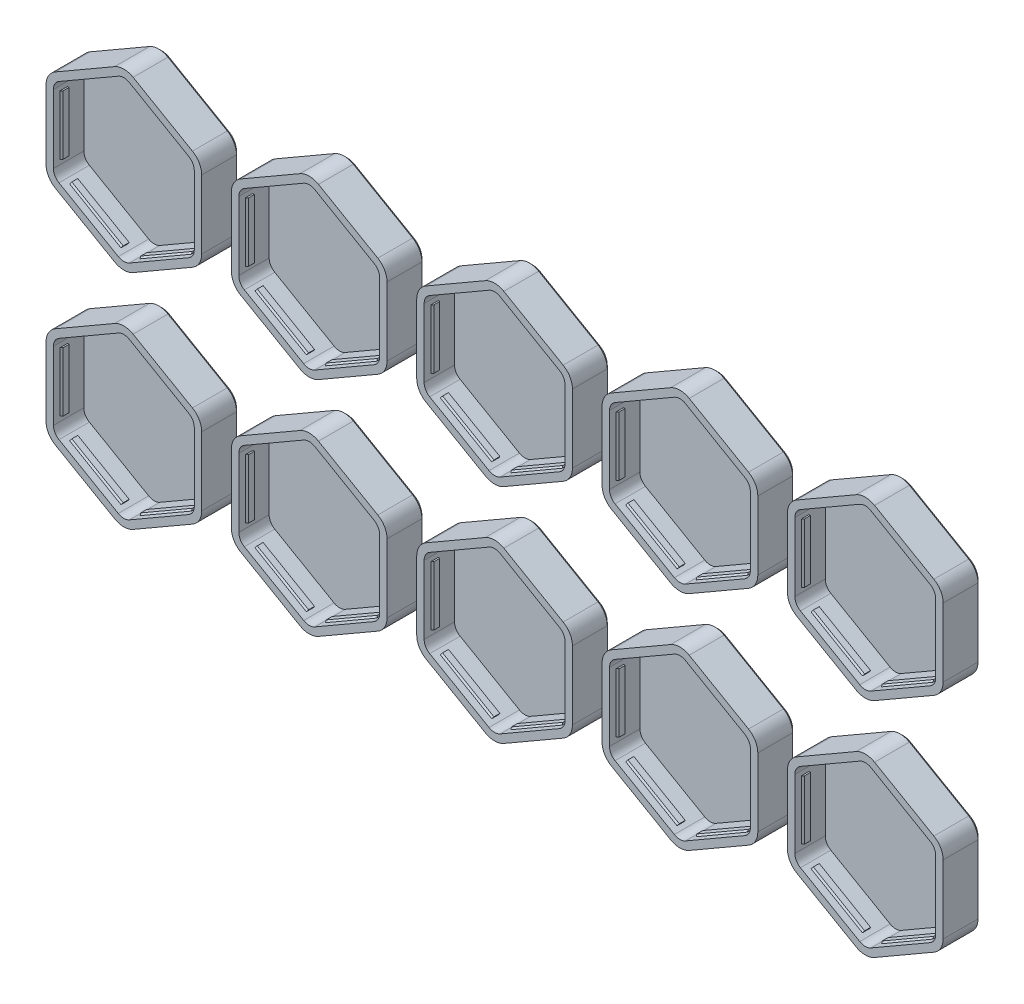
SolidWorks part; units mm, degrees
ref_plane "前视基准面" through (0, 0, 0) normal (0, 0, 1) x (1, 0, 0)
ref_plane "上视基准面" through (0, 0, 0) normal (0, 1, 0) x (1, 0, 0)
ref_plane "右视基准面" through (0, 0, 0) normal (1, 0, 0) x (0, 0, -1)
sketch "草图1" plane through (0, 0, 0) normal (0, 0, 1) x (1, 0, 0)
  line L0 (-36.9964, 0) -> (135.3315, 0) construction
  line L8 (-20.6295, 11.6625) -> (-28.6295, 7.0437)
  line L9 (-30.0295, 4.6188) -> (-30.0295, -4.6188)
  line L10 (-28.6295, -7.0437) -> (-20.6295, -11.6625)
  line L11 (-17.8295, -11.6625) -> (-9.8295, -7.0437)
  line L12 (-8.4295, -4.6188) -> (-8.4295, 4.6188)
  line L13 (-9.8295, 7.0437) -> (-17.8295, 11.6625)
  line L14 (17.8795, 11.5759) -> (9.8795, 6.9571)
  line L15 (8.5295, 4.6188) -> (8.5295, -4.6188)
  line L16 (9.8795, -6.9571) -> (17.8795, -11.5759)
  line L17 (20.5795, -11.5759) -> (28.5795, -6.9571)
  line L18 (29.9295, -4.6188) -> (29.9295, 4.6188)
  line L19 (28.5795, 6.9571) -> (20.5795, 11.5759)
  line L20 (53.7572, 11.4893) -> (45.7572, 6.8705)
  line L21 (44.4572, 4.6188) -> (44.4572, -4.6188)
  line L22 (45.7572, -6.8705) -> (53.7572, -11.4893)
  line L23 (56.3572, -11.4893) -> (64.3572, -6.8705)
  line L24 (65.6572, -4.6188) -> (65.6572, 4.6188)
  line L25 (64.3572, 6.8705) -> (56.3572, 11.4893)
  line L26 (86.3289, 11.4027) -> (78.3289, 6.7839)
  line L27 (77.0789, 4.6188) -> (77.0789, -4.6188)
  line L28 (78.3289, -6.7839) -> (86.3289, -11.4027)
  line L29 (88.8289, -11.4027) -> (96.8289, -6.7839)
  line L30 (98.0789, -4.6188) -> (98.0789, 4.6188)
  line L31 (96.8289, 6.7839) -> (88.8289, 11.4027)
  circle A0 centre (-19.2295, 0) radius 10.8 construction
  circle A1 centre (19.2295, 0) radius 10.7 construction
  circle A2 centre (55.0572, 0) radius 10.6 construction
  circle A3 centre (87.5789, 0) radius 10.5 construction
  arc A4 (-8.4295, 4.6188) -> (-9.8295, 7.0437) centre (-11.2295, 4.6188) ccw
  arc A5 (-8.4295, -4.6188) -> (-9.8295, -7.0437) centre (-11.2295, -4.6188) cw
  arc A6 (-17.8295, -11.6625) -> (-20.6295, -11.6625) centre (-19.2295, -9.2376) cw
  arc A7 (-28.6295, -7.0437) -> (-30.0295, -4.6188) centre (-27.2295, -4.6188) cw
  arc A8 (-28.6295, 7.0437) -> (-30.0295, 4.6188) centre (-27.2295, 4.6188) ccw
  arc A9 (-20.6295, 11.6625) -> (-17.8295, 11.6625) centre (-19.2295, 9.2376) cw
  arc A10 (29.9295, 4.6188) -> (28.5795, 6.9571) centre (27.2295, 4.6188) ccw
  arc A11 (29.9295, -4.6188) -> (28.5795, -6.9571) centre (27.2295, -4.6188) cw
  arc A12 (20.5795, -11.5759) -> (17.8795, -11.5759) centre (19.2295, -9.2376) cw
  arc A13 (9.8795, -6.9571) -> (8.5295, -4.6188) centre (11.2295, -4.6188) cw
  arc A14 (8.5295, 4.6188) -> (9.8795, 6.9571) centre (11.2295, 4.6188) cw
  arc A15 (20.5795, 11.5759) -> (17.8795, 11.5759) centre (19.2295, 9.2376) ccw
  arc A16 (53.7572, 11.4893) -> (56.3572, 11.4893) centre (55.0572, 9.2376) cw
  arc A17 (65.6572, 4.6188) -> (64.3572, 6.8705) centre (63.0572, 4.6188) ccw
  arc A18 (65.6572, -4.6188) -> (64.3572, -6.8705) centre (63.0572, -4.6188) cw
  arc A19 (56.3572, -11.4893) -> (53.7572, -11.4893) centre (55.0572, -9.2376) cw
  arc A20 (45.7572, -6.8705) -> (44.4572, -4.6188) centre (47.0572, -4.6188) cw
  arc A21 (44.4572, 4.6188) -> (45.7572, 6.8705) centre (47.0572, 4.6188) cw
  arc A22 (98.0789, 4.6188) -> (96.8289, 6.7839) centre (95.5789, 4.6188) ccw
  arc A23 (98.0789, -4.6188) -> (96.8289, -6.7839) centre (95.5789, -4.6188) cw
  arc A24 (88.8289, -11.4027) -> (86.3289, -11.4027) centre (87.5789, -9.2376) cw
  arc A25 (78.3289, -6.7839) -> (77.0789, -4.6188) centre (79.5789, -4.6188) cw
  arc A26 (77.0789, 4.6188) -> (78.3289, 6.7839) centre (79.5789, 4.6188) cw
  arc A27 (88.8289, 11.4027) -> (86.3289, 11.4027) centre (87.5789, 9.2376) ccw
  dimension "D1" = 21.6
  dimension "D2" = 21.4
  dimension "D3" = 21.2
  dimension "D4" = 21
  dimension "D5" = 2.8
  dimension "D6" = 2.7
  dimension "D7" = 2.6
  dimension "D8" = 2.5
extrude "凸台-拉伸1" add sketch "草图1" along normal blind 4.5
sketch "草图2" plane through (0, 0, 4.5) normal (0, 0, 1) x (1, 0, 0)
  line L0 (-30.0295, 0) -> (-8.4295, 0) construction
  line L1 (-30.0295, 4.6188) -> (-30.0295, -4.6188) construction
  line L2 (-8.4295, -4.6188) -> (-8.4295, 4.6188) construction
  line L3 (8.5295, 0) -> (29.9295, 0) construction
  line L4 (8.5295, 4.6188) -> (8.5295, -4.6188) construction
  line L5 (29.9295, -4.6188) -> (29.9295, 4.6188) construction
  line L6 (44.4572, 0) -> (65.6572, 0) construction
  line L7 (44.4572, 4.6188) -> (44.4572, -4.6188) construction
  line L8 (65.6572, -4.6188) -> (65.6572, 4.6188) construction
  line L9 (77.0789, 0) -> (98.0789, 0) construction
  line L10 (77.0789, 4.6188) -> (77.0789, -4.6188) construction
  line L11 (98.0789, -4.6188) -> (98.0789, 4.6188) construction
  line L12 (-9.8295, 7.0437) -> (-17.8295, 11.6625) construction
  line L13 (-20.1295, 10.7965) -> (-28.1295, 6.1776)
  line L14 (-29.0295, 4.6188) -> (-29.0295, -4.6188)
  line L15 (-28.1295, -6.1776) -> (-20.1295, -10.7965)
  line L16 (-18.3295, -10.7965) -> (-10.3295, -6.1776)
  line L17 (-9.4295, -4.6188) -> (-9.4295, 4.6188)
  line L18 (-10.3295, 6.1776) -> (-18.3295, 10.7965)
  line L19 (18.3795, 10.7098) -> (10.3795, 6.091)
  line L20 (9.5295, 4.6188) -> (9.5295, -4.6188)
  line L21 (10.3795, -6.091) -> (18.3795, -10.7098)
  line L22 (20.0795, -10.7098) -> (28.0795, -6.091)
  line L23 (28.9295, -4.6188) -> (28.9295, 4.6188)
  line L24 (28.0795, 6.091) -> (20.0795, 10.7098)
  line L25 (54.2572, 10.6232) -> (46.2572, 6.0044)
  line L26 (45.4572, 4.6188) -> (45.4572, -4.6188)
  line L27 (46.2572, -6.0044) -> (54.2572, -10.6232)
  line L28 (55.8572, -10.6232) -> (63.8572, -6.0044)
  line L29 (64.6572, -4.6188) -> (64.6572, 4.6188)
  line L30 (63.8572, 6.0044) -> (55.8572, 10.6232)
  line L31 (86.8289, 10.5366) -> (78.8289, 5.9178)
  line L32 (78.0789, 4.6188) -> (78.0789, -4.6188)
  line L33 (78.8289, -5.9178) -> (86.8289, -10.5366)
  line L34 (88.3289, -10.5366) -> (96.3289, -5.9178)
  line L35 (97.0789, -4.6188) -> (97.0789, 4.6188)
  line L36 (96.3289, 5.9178) -> (88.3289, 10.5366)
  circle A0 centre (-19.2295, 0) radius 9.8 construction
  circle A1 centre (19.2295, 0) radius 9.7 construction
  circle A2 centre (55.0572, 0) radius 9.6 construction
  circle A3 centre (87.5789, 0) radius 9.5 construction
  arc A4 (-9.4295, 4.6188) -> (-10.3295, 6.1776) centre (-11.2295, 4.6188) ccw
  arc A5 (-9.4295, -4.6188) -> (-10.3295, -6.1776) centre (-11.2295, -4.6188) cw
  arc A6 (-18.3295, -10.7965) -> (-20.1295, -10.7965) centre (-19.2295, -9.2376) cw
  arc A7 (-28.1295, -6.1776) -> (-29.0295, -4.6188) centre (-27.2295, -4.6188) cw
  arc A8 (-29.0295, 4.6188) -> (-28.1295, 6.1776) centre (-27.2295, 4.6188) cw
  arc A9 (-18.3295, 10.7965) -> (-20.1295, 10.7965) centre (-19.2295, 9.2376) ccw
  arc A10 (9.5295, -4.6188) -> (10.3795, -6.091) centre (11.2295, -4.6188) ccw
  arc A11 (18.3795, -10.7098) -> (20.0795, -10.7098) centre (19.2295, -9.2376) ccw
  arc A12 (28.0795, -6.091) -> (28.9295, -4.6188) centre (27.2295, -4.6188) ccw
  arc A13 (28.9295, 4.6188) -> (28.0795, 6.091) centre (27.2295, 4.6188) ccw
  arc A14 (20.0795, 10.7098) -> (18.3795, 10.7098) centre (19.2295, 9.2376) ccw
  arc A15 (10.3795, 6.091) -> (9.5295, 4.6188) centre (11.2295, 4.6188) ccw
  arc A16 (55.8572, 10.6232) -> (54.2572, 10.6232) centre (55.0572, 9.2376) ccw
  arc A17 (64.6572, 4.6188) -> (63.8572, 6.0044) centre (63.0572, 4.6188) ccw
  arc A18 (64.6572, -4.6188) -> (63.8572, -6.0044) centre (63.0572, -4.6188) cw
  arc A19 (55.8572, -10.6232) -> (54.2572, -10.6232) centre (55.0572, -9.2376) cw
  arc A20 (46.2572, -6.0044) -> (45.4572, -4.6188) centre (47.0572, -4.6188) cw
  arc A21 (45.4572, 4.6188) -> (46.2572, 6.0044) centre (47.0572, 4.6188) cw
  arc A22 (97.0789, 4.6188) -> (96.3289, 5.9178) centre (95.5789, 4.6188) ccw
  arc A23 (97.0789, -4.6188) -> (96.3289, -5.9178) centre (95.5789, -4.6188) cw
  arc A24 (88.3289, -10.5366) -> (86.8289, -10.5366) centre (87.5789, -9.2376) cw
  arc A25 (78.8289, -5.9178) -> (78.0789, -4.6188) centre (79.5789, -4.6188) cw
  arc A26 (78.0789, 4.6188) -> (78.8289, 5.9178) centre (79.5789, 4.6188) cw
  arc A27 (88.3289, 10.5366) -> (86.8289, 10.5366) centre (87.5789, 9.2376) ccw
  dimension "D5" = 1.8
  dimension "D6" = 1.7
  dimension "D7" = 1.6
  dimension "D8" = 1.5
  dimension "D1" = 1
  dimension "D2" = 1
  dimension "D3" = 1
  dimension "D4" = 1
extrude "切除-拉伸1" cut sketch "草图2" against normal blind 4.1
sketch "草图4" plane through (0, 0, 0.4) normal (0, 0, 1) x (1, 0, 0)
  line L0 (-23.9981, -1.2437) -> (-14.5907, -1.2437) construction
  line L1 (14.4741, -2.5074) -> (25.7068, -2.5074) construction
  line L2 (50.8401, -2.5074) -> (61.9324, -2.5074) construction
  line L3 (80.6069, -3.6306) -> (93.5246, -3.6306) construction
  text T0 "   1"
  text T1 "   2"
  text T2 "  3"
  text T3 "   4"
extrude "切除-拉伸2" cut sketch "草图4" against normal blind 4.1
ref_plane "基准面1" through (0, 0, 2.6) normal (0, 0, 1) x (1, 0, 0)
sketch "草图5" plane through (0, 0, 0.4) normal (0, 0, 1) x (1, 0, 0)
  line L0 (-20.1295, 10.7965) -> (-28.1295, 6.1776) construction
  line L1 (-20.6654, 10.487) -> (-27.5936, 6.487)
  line L7 (-20.5654, 10.3138) -> (-27.4936, 6.3138)
  line L16 (-19.2295, 0) -> (-24.6295, 9.3531) construction
  line L17 (-20.6295, 11.6625) -> (-28.6295, 7.0437) construction
  line L18 (-24.6295, 9.3531) -> (-27.3183, 14.0102) construction
  line L19 (-27.3183, 14.0102) -> (-14.3295, -8.487) construction
  line L20 (-27.5936, 6.487) -> (-27.4936, 6.3138)
  line L21 (-20.6654, 10.487) -> (-20.5654, 10.3138)
  line L22 (-10.8654, 6.487) -> (-17.7936, 10.487)
  line L23 (-10.9654, 6.3138) -> (-17.8936, 10.3138)
  line L24 (-17.7936, 10.487) -> (-17.8936, 10.3138)
  line L25 (-10.8654, 6.487) -> (-10.9654, 6.3138)
  line L26 (-9.4295, -4) -> (-9.4295, 4)
  line L27 (-9.6295, -4) -> (-9.6295, 4)
  line L28 (-9.4295, 4) -> (-9.6295, 4)
  line L29 (-9.4295, -4) -> (-9.6295, -4)
  line L30 (-17.7936, -10.487) -> (-10.8654, -6.487)
  line L31 (-17.8936, -10.3138) -> (-10.9654, -6.3138)
  line L32 (-10.8654, -6.487) -> (-10.9654, -6.3138)
  line L33 (-17.7936, -10.487) -> (-17.8936, -10.3138)
  line L34 (-27.5936, -6.487) -> (-20.6654, -10.487)
  line L35 (-27.4936, -6.3138) -> (-20.5654, -10.3138)
  line L36 (-20.6654, -10.487) -> (-20.5654, -10.3138)
  line L37 (-27.5936, -6.487) -> (-27.4936, -6.3138)
  line L38 (-29.0295, 4) -> (-29.0295, -4)
  line L39 (-28.8295, 4) -> (-28.8295, -4)
  line L40 (-29.0295, -4) -> (-28.8295, -4)
  line L41 (-29.0295, 4) -> (-28.8295, 4)
  arc A0 (-12.7237, 7.329) -> (-16.1354, 9.2987) centre (-19.2295, 0) ccw construction
  arc A1 (-9.6295, -1.9698) -> (-9.6295, 1.9698) centre (-19.2295, 0) ccw construction
  arc A2 (-22.3237, 9.2987) -> (-25.7354, 7.329) centre (-19.2295, 0) ccw construction
  arc A3 (-16.1354, -9.2987) -> (-12.7237, -7.329) centre (-19.2295, 0) ccw construction
  arc A5 (-25.7354, -7.329) -> (-22.3237, -9.2987) centre (-19.2295, 0) ccw construction
  arc A6 (-28.8295, 1.9698) -> (-28.8295, -1.9698) centre (-19.2295, 0) ccw construction
  dimension "D1" = 0.2
  dimension "D2" = 4
  dimension "D3" = 4
  dimension "D4" = 6
extrude "凸台-拉伸2" add sketch "草图5" along normal blind 1 from surface starting at plane "基准面1"
chamfer "倒角1" distance 0.2 angle 45 6 edges at (-28.8295, 0, 3.6) (-24.0295, -8.3138, 3.6) (-14.4295, -8.3138, 3.6) (-9.6295, 0, 3.6) (-14.4295, 8.3138, 3.6) (-24.0295, 8.3138, 3.6)
sketch "草图6" plane through (0, 0, 2.6) normal (0, 0, 1) x (1, 0, 0)
  line L0 (9.5295, 0) -> (28.9295, 0) construction
  line L1 (9.5295, 4.6188) -> (9.5295, -4.6188) construction
  line L2 (28.9295, -4.6188) -> (28.9295, 4.6188) construction
  line L3 (10.8154, 6.5737) -> (11.0154, 6.2272)
  line L4 (9.3295, -4) -> (9.7295, -4)
  line L5 (9.3295, -4) -> (9.3295, 4)
  line L6 (9.3295, 4) -> (9.7295, 4)
  line L7 (9.7295, -4) -> (9.7295, 4)
  line L8 (9.3295, -4) -> (9.7295, 4) construction
  line L9 (9.3295, 4) -> (9.7295, -4) construction
  line L10 (10.8154, 6.5737) -> (17.7436, 10.5737)
  line L11 (17.7436, 10.5737) -> (17.9436, 10.2272)
  line L12 (11.0154, 6.2272) -> (17.9436, 10.2272)
  line L13 (10.8154, 6.5737) -> (17.9436, 10.2272) construction
  line L14 (17.7436, 10.5737) -> (11.0154, 6.2272) construction
  line L15 (20.7154, 10.5737) -> (20.5154, 10.2272)
  line L16 (20.7154, 10.5737) -> (27.6436, 6.5737)
  line L17 (27.6436, 6.5737) -> (27.4436, 6.2272)
  line L18 (20.5154, 10.2272) -> (27.4436, 6.2272)
  line L19 (20.7154, 10.5737) -> (27.4436, 6.2272) construction
  line L20 (27.6436, 6.5737) -> (20.5154, 10.2272) construction
  line L21 (29.1295, 4) -> (28.7295, 4)
  line L22 (29.1295, 4) -> (29.1295, -4)
  line L23 (29.1295, -4) -> (28.7295, -4)
  line L24 (28.7295, 4) -> (28.7295, -4)
  line L25 (29.1295, 4) -> (28.7295, -4) construction
  line L26 (29.1295, -4) -> (28.7295, 4) construction
  line L27 (27.6436, -6.5737) -> (27.4436, -6.2272)
  line L28 (27.6436, -6.5737) -> (20.7154, -10.5737)
  line L29 (20.7154, -10.5737) -> (20.5154, -10.2272)
  line L30 (27.4436, -6.2272) -> (20.5154, -10.2272)
  line L31 (27.6436, -6.5737) -> (20.5154, -10.2272) construction
  line L32 (20.7154, -10.5737) -> (27.4436, -6.2272) construction
  line L33 (17.7436, -10.5737) -> (17.9436, -10.2272)
  line L34 (17.7436, -10.5737) -> (10.8154, -6.5737)
  line L35 (10.8154, -6.5737) -> (11.0154, -6.2272)
  line L36 (17.9436, -10.2272) -> (11.0154, -6.2272)
  line L37 (17.7436, -10.5737) -> (11.0154, -6.2272) construction
  line L38 (10.8154, -6.5737) -> (17.9436, -10.2272) construction
  point P6 (19.2295, 0)
  dimension "D1" = 8
  dimension "D2" = 0.4
extrude "凸台-拉伸3" add sketch "草图6" along normal blind 1
chamfer "倒角4" distance 0.2 angle 45 6 edges at (14.4795, -8.2272, 3.6) (23.9795, -8.2272, 3.6) (28.7295, 0, 3.6) (23.9795, 8.2272, 3.6) (9.7295, 0, 3.6) (14.4795, 8.2272, 3.6)
sketch "草图7" plane through (0, 0, 2.6) normal (0, 0, 1) x (1, 0, 0)
  line L0 (45.4572, 0) -> (64.6572, 0) construction
  line L1 (45.4572, 4.6188) -> (45.4572, -4.6188) construction
  line L2 (64.6572, -4.6188) -> (64.6572, 4.6188) construction
  line L3 (46.6931, 6.487) -> (46.8931, 6.1406)
  line L4 (45.2572, -4) -> (45.6572, -4)
  line L5 (45.2572, -4) -> (45.2572, 4)
  line L6 (45.2572, 4) -> (45.6572, 4)
  line L7 (45.6572, -4) -> (45.6572, 4)
  line L8 (45.2572, -4) -> (45.6572, 4) construction
  line L9 (45.2572, 4) -> (45.6572, -4) construction
  line L10 (46.6931, 6.487) -> (53.6213, 10.487)
  line L11 (53.6213, 10.487) -> (53.8213, 10.1406)
  line L12 (46.8931, 6.1406) -> (53.8213, 10.1406)
  line L13 (50.2572, 8.3138) -> (59.8572, -8.3138) construction
  line L14 (46.6931, 6.487) -> (53.8213, 10.1406) construction
  line L15 (53.6213, 10.487) -> (46.8931, 6.1406) construction
  line L16 (56.4931, 10.487) -> (56.2931, 10.1406)
  line L17 (56.4931, 10.487) -> (63.4213, 6.487)
  line L18 (63.4213, 6.487) -> (63.2213, 6.1406)
  line L19 (56.2931, 10.1406) -> (63.2213, 6.1406)
  line L20 (59.8572, 8.3138) -> (50.2572, -8.3138) construction
  line L21 (56.4931, 10.487) -> (63.2213, 6.1406) construction
  line L22 (63.4213, 6.487) -> (56.2931, 10.1406) construction
  line L23 (64.8572, 4) -> (64.4572, 4)
  line L24 (64.8572, 4) -> (64.8572, -4)
  line L25 (64.8572, -4) -> (64.4572, -4)
  line L26 (64.4572, 4) -> (64.4572, -4)
  line L27 (64.6572, 0) -> (45.4572, 0) construction
  line L28 (64.8572, 4) -> (64.4572, -4) construction
  line L29 (64.8572, -4) -> (64.4572, 4) construction
  line L30 (63.4213, -6.487) -> (63.2213, -6.1406)
  line L31 (63.4213, -6.487) -> (56.4931, -10.487)
  line L32 (56.4931, -10.487) -> (56.2931, -10.1406)
  line L33 (63.2213, -6.1406) -> (56.2931, -10.1406)
  line L34 (59.8572, -8.3138) -> (50.2572, 8.3138) construction
  line L35 (63.4213, -6.487) -> (56.2931, -10.1406) construction
  line L36 (56.4931, -10.487) -> (63.2213, -6.1406) construction
  line L37 (53.6213, -10.487) -> (53.8213, -10.1406)
  line L38 (53.6213, -10.487) -> (46.6931, -6.487)
  line L39 (46.6931, -6.487) -> (46.8931, -6.1406)
  line L40 (53.8213, -10.1406) -> (46.8931, -6.1406)
  line L41 (50.2572, -8.3138) -> (59.8572, 8.3138) construction
  line L42 (53.6213, -10.487) -> (46.8931, -6.1406) construction
  line L43 (46.6931, -6.487) -> (53.8213, -10.1406) construction
  point P10 (55.0572, 0)
  dimension "D1" = 8
  dimension "D2" = 0.4
extrude "凸台-拉伸4" add sketch "草图7" along normal blind 1
chamfer "倒角5" distance 0.2 angle 45 6 edges at (50.3572, -8.1406, 3.6) (59.7572, -8.1406, 3.6) (64.4572, 0, 3.6) (59.7572, 8.1406, 3.6) (50.3572, 8.1406, 3.6) (45.6572, 0, 3.6)
sketch "草图8" plane through (0, 0, 2.6) normal (0, 0, 1) x (1, 0, 0)
  line L0 (78.0789, 0) -> (97.0789, 0) construction
  line L1 (78.0789, 4.6188) -> (78.0789, -4.6188) construction
  line L2 (97.0789, -4.6188) -> (97.0789, 4.6188) construction
  line L3 (79.2648, 6.4004) -> (79.4648, 6.054)
  line L4 (77.8789, -4) -> (78.2789, -4)
  line L5 (77.8789, -4) -> (77.8789, 4)
  line L6 (77.8789, 4) -> (78.2789, 4)
  line L7 (78.2789, -4) -> (78.2789, 4)
  line L8 (77.8789, -4) -> (78.2789, 4) construction
  line L9 (77.8789, 4) -> (78.2789, -4) construction
  line L10 (79.2648, 6.4004) -> (86.193, 10.4004)
  line L11 (86.193, 10.4004) -> (86.393, 10.054)
  line L12 (79.4648, 6.054) -> (86.393, 10.054)
  line L13 (82.8289, 8.2272) -> (92.3289, -8.2272) construction
  line L14 (79.2648, 6.4004) -> (86.393, 10.054) construction
  line L15 (86.193, 10.4004) -> (79.4648, 6.054) construction
  line L16 (88.9648, 10.4004) -> (88.7648, 10.054)
  line L17 (88.9648, 10.4004) -> (95.893, 6.4004)
  line L18 (95.893, 6.4004) -> (95.693, 6.054)
  line L19 (88.7648, 10.054) -> (95.693, 6.054)
  line L20 (92.3289, 8.2272) -> (82.8289, -8.2272) construction
  line L21 (88.9648, 10.4004) -> (95.693, 6.054) construction
  line L22 (95.893, 6.4004) -> (88.7648, 10.054) construction
  line L23 (97.2789, 4) -> (96.8789, 4)
  line L24 (97.2789, 4) -> (97.2789, -4)
  line L25 (97.2789, -4) -> (96.8789, -4)
  line L26 (96.8789, 4) -> (96.8789, -4)
  line L27 (97.0789, 0) -> (78.0789, 0) construction
  line L28 (97.2789, 4) -> (96.8789, -4) construction
  line L29 (97.2789, -4) -> (96.8789, 4) construction
  line L30 (95.893, -6.4004) -> (95.693, -6.054)
  line L31 (95.893, -6.4004) -> (88.9648, -10.4004)
  line L32 (88.9648, -10.4004) -> (88.7648, -10.054)
  line L33 (95.693, -6.054) -> (88.7648, -10.054)
  line L34 (92.3289, -8.2272) -> (82.8289, 8.2272) construction
  line L35 (95.893, -6.4004) -> (88.7648, -10.054) construction
  line L36 (88.9648, -10.4004) -> (95.693, -6.054) construction
  line L37 (86.193, -10.4004) -> (86.393, -10.054)
  line L38 (86.193, -10.4004) -> (79.2648, -6.4004)
  line L39 (79.2648, -6.4004) -> (79.4648, -6.054)
  line L40 (86.393, -10.054) -> (79.4648, -6.054)
  line L41 (82.8289, -8.2272) -> (92.3289, 8.2272) construction
  line L42 (86.193, -10.4004) -> (79.4648, -6.054) construction
  line L43 (79.2648, -6.4004) -> (86.393, -10.054) construction
  point P6 (87.5789, 0)
  dimension "D1" = 8
  dimension "D2" = 0.4
extrude "凸台-拉伸5" add sketch "草图8" along normal blind 1
chamfer "倒角6" distance 0.2 angle 45 6 edges at (82.9289, -8.054, 3.6) (92.2289, -8.054, 3.6) (96.8789, 0, 3.6) (92.2289, 8.054, 3.6) (82.9289, 8.054, 3.6) (78.2789, 0, 3.6)
sketch "草图9" plane through (0, 0, 0) normal (0, 0, 1) x (1, 0, 0)
  line L0 (-19.2295, 11.0376) -> (-19.2295, -51.6908) construction
  line L1 (-19.2295, -39.2072) -> (114.7779, -39.2072) construction
  line L2 (19.2295, 10.9376) -> (19.2295, -51.6908) construction
  line L3 (55.0572, 10.8376) -> (55.0572, -53.0164) construction
  line L4 (87.5789, 10.7376) -> (87.5789, -51.6908) construction
  line L6 (-19.2295, -28.0066) -> (-28.9295, -33.6069)
  line L7 (-28.9295, -33.6069) -> (-28.9295, -44.8075)
  line L8 (-28.9295, -44.8075) -> (-19.2295, -50.4078)
  line L9 (-19.2295, -50.4078) -> (-9.5295, -44.8075)
  line L10 (-9.5295, -44.8075) -> (-9.5295, -33.6069)
  line L11 (-9.5295, -33.6069) -> (-19.2295, -28.0066)
  line L12 (19.2295, -28.1221) -> (9.6295, -33.6647)
  line L13 (9.6295, -33.6647) -> (9.6295, -44.7498)
  line L14 (9.6295, -44.7498) -> (19.2295, -50.2924)
  line L15 (19.2295, -50.2924) -> (28.8295, -44.7498)
  line L16 (28.8295, -44.7498) -> (28.8295, -33.6647)
  line L17 (28.8295, -33.6647) -> (19.2295, -28.1221)
  line L18 (55.0572, -28.2376) -> (45.5572, -33.7224)
  line L19 (45.5572, -33.7224) -> (45.5572, -44.6921)
  line L20 (45.5572, -44.6921) -> (55.0572, -50.1769)
  line L21 (55.0572, -50.1769) -> (64.5572, -44.6921)
  line L22 (64.5572, -44.6921) -> (64.5572, -33.7224)
  line L23 (64.5572, -33.7224) -> (55.0572, -28.2376)
  line L24 (87.5789, -28.3531) -> (78.1789, -33.7802)
  line L25 (78.1789, -33.7802) -> (78.1789, -44.6343)
  line L26 (78.1789, -44.6343) -> (87.5789, -50.0614)
  line L27 (87.5789, -50.0614) -> (96.9789, -44.6343)
  line L28 (96.9789, -44.6343) -> (96.9789, -33.7802)
  line L29 (96.9789, -33.7802) -> (87.5789, -28.3531)
  arc A0 (-18.3295, 10.7965) -> (-20.1295, 10.7965) centre (-19.2295, 9.2376) ccw construction
  arc A1 (20.0795, 10.7098) -> (18.3795, 10.7098) centre (19.2295, 9.2376) ccw construction
  arc A2 (55.8572, 10.6232) -> (54.2572, 10.6232) centre (55.0572, 9.2376) ccw construction
  arc A3 (88.3289, 10.5366) -> (86.8289, 10.5366) centre (87.5789, 9.2376) ccw construction
  circle A4 centre (-19.2295, -39.2072) radius 9.7 construction
  circle A5 centre (19.2295, -39.2072) radius 9.6 construction
  circle A6 centre (55.0572, -39.2072) radius 9.5 construction
  circle A7 centre (87.5789, -39.2072) radius 9.4 construction
  dimension "D1" = 19.4
  dimension "D2" = 19.2
  dimension "D3" = 19
  dimension "D4" = 18.8
extrude "凸台-拉伸6" add sketch "草图9" along normal blind 2 separate body
sketch "草图10" plane through (0, 0, 2) normal (0, 0, 1) x (1, 0, 0)
  line L0 (-28.9295, -39.2072) -> (-21.4295, -39.2072) construction
  line L2 (-9.5295, -44.8075) -> (-9.5295, -33.6069) construction
  line L3 (-19.8995, -39.8772) -> (-21.4295, -39.8772)
  line L6 (-19.8995, -38.5372) -> (-21.4295, -38.5372)
  line L12 (-19.8995, -38.5372) -> (-19.8995, -37.0072)
  line L13 (-19.8995, -41.4072) -> (-18.5595, -41.4072)
  line L14 (-19.8995, -41.4072) -> (-19.8995, -39.8772)
  line L15 (-19.8995, -37.0072) -> (-18.5595, -37.0072)
  line L16 (-18.5595, -41.4072) -> (-18.5595, -39.8772)
  line L19 (-17.0295, -38.5372) -> (-18.5595, -38.5372)
  line L20 (-17.0295, -38.5372) -> (-17.0295, -39.8772)
  line L21 (-17.0295, -39.8772) -> (-18.5595, -39.8772)
  line L22 (-21.4295, -38.5372) -> (-21.4295, -39.8772)
  line L36 (-18.5595, -38.5372) -> (-18.5595, -37.0072)
  line L41 (-17.0295, -39.2072) -> (-9.5295, -39.2072) construction
  circle A0 centre (-19.2295, -39.2072) radius 2.55
extrude "凸台-拉伸7" add sketch "草图10" along normal blind 3
fillet "圆角1" radius 0.2 12 edges at (-18.5595, -41.4072, 3.5) (-19.8995, -41.4072, 3.5) (-19.8995, -39.8772, 3.5) (-18.5595, -39.8772, 3.5) (-17.0295, -39.8772, 3.5) (-17.0295, -38.5372, 3.5) (-18.5595, -38.5372, 3.5) (-19.8995, -38.5372, 3.5) (-21.4295, -39.8772, 3.5) (-21.4295, -38.5372, 3.5) (-18.5595, -37.0072, 3.5) (-19.8995, -37.0072, 3.5)
fillet "圆角2" radius 1.7 6 edges at (-19.2295, -50.4078, 1) (-9.5295, -44.8075, 1) (-9.5295, -33.6069, 1) (-19.2295, -28.0066, 1) (-28.9295, -33.6069, 1) (-28.9295, -44.8075, 1)
fillet "圆角3" radius 1.6 6 edges at (19.2295, -50.2924, 1) (28.8295, -44.7498, 1) (28.8295, -33.6647, 1) (19.2295, -28.1221, 1) (9.6295, -33.6647, 1) (9.6295, -44.7498, 1)
fillet "圆角4" radius 1.5 6 edges at (55.0572, -50.1769, 1) (45.5572, -44.6921, 1) (45.5572, -33.7224, 1) (55.0572, -28.2376, 1) (64.5572, -33.7224, 1) (64.5572, -44.6921, 1)
fillet "圆角5" radius 1.4 6 edges at (87.5789, -50.0614, 1) (78.1789, -44.6343, 1) (78.1789, -33.7802, 1) (87.5789, -28.3531, 1) (96.9789, -33.7802, 1) (96.9789, -44.6343, 1)
chamfer "倒角8" distance 0.6 angle 45 12 edges at (-9.5295, -39.2072, 0) (-9.7573, -33.7384, 0) (-9.7573, -44.676, 0) (-14.3795, -30.8068, 0) (-14.3795, -47.6077, 0) (-19.2295, -28.2696, 0) (-19.2295, -50.1448, 0) (-24.0795, -30.8068, 0) (-24.0795, -47.6077, 0) (-28.7018, -33.7384, 0) (-28.7018, -44.676, 0) (-28.9295, -39.2072, 0)
chamfer "倒角9" distance 0.6 angle 45 12 edges at (28.8295, -39.2072, 0) (28.6152, -33.7884, 0) (28.6152, -44.626, 0) (24.0295, -30.8934, 0) (24.0295, -47.5211, 0) (19.2295, -28.3696, 0) (19.2295, -50.0448, 0) (14.4295, -30.8934, 0) (14.4295, -47.5211, 0) (9.8439, -33.7884, 0) (9.8439, -44.626, 0) (9.6295, -39.2072, 0)
chamfer "倒角10" distance 0.6 angle 45 12 edges at (64.5572, -39.2072, 0) (64.3562, -33.8384, 0) (64.3562, -44.576, 0) (59.8072, -30.98, 0) (59.8072, -47.4345, 0) (55.0572, -28.4696, 0) (55.0572, -49.9448, 0) (50.3072, -30.98, 0) (50.3072, -47.4345, 0) (45.7581, -33.8384, 0) (45.7581, -44.576, 0) (45.5572, -39.2072, 0)
chamfer "倒角11" distance 0.6 angle 45 12 edges at (96.9789, -39.2072, 0) (96.7914, -33.8884, 0) (96.7914, -44.526, 0) (92.2789, -31.0666, 0) (92.2789, -47.3479, 0) (87.5789, -28.5696, 0) (87.5789, -49.8448, 0) (82.8789, -31.0666, 0) (82.8789, -47.3479, 0) (78.3665, -33.8884, 0) (78.3665, -44.526, 0) (78.1789, -39.2072, 0)
chamfer "倒角12" distance 0.4 angle 45 12 edges at (77.4139, 5.8688, 0) (77.0789, 0, 0) (82.3289, 9.0933, 0) (77.4139, -5.8688, 0) (87.5789, 11.7376, 0) (82.3289, -9.0933, 0) (92.8289, 9.0933, 0) (87.5789, -11.7376, 0) (97.744, 5.8688, 0) (92.8289, -9.0933, 0) (98.0789, 0, 0) (97.744, -5.8688, 0)
chamfer "倒角13" distance 0.4 angle 45 12 edges at (44.4572, 0, 0) (44.8055, -5.9188, 0) (44.8055, 5.9188, 0) (49.7572, -9.1799, 0) (49.7572, 9.1799, 0) (55.0572, -11.8376, 0) (55.0572, 11.8376, 0) (60.3572, -9.1799, 0) (60.3572, 9.1799, 0) (65.3088, -5.9188, 0) (65.3088, 5.9188, 0) (65.6572, 0, 0)
chamfer "倒角14" distance 0.4 angle 45 12 edges at (8.8913, 5.9688, 0) (8.5295, 0, 0) (13.8795, 9.2665, 0) (8.8913, -5.9688, 0) (19.2295, 11.9376, 0) (13.8795, -9.2665, 0) (24.5795, 9.2665, 0) (19.2295, -11.9376, 0) (29.5678, 5.9688, 0) (24.5795, -9.2665, 0) (29.9295, 0, 0) (29.5678, -5.9688, 0)
chamfer "倒角15" distance 0.4 angle 45 12 edges at (-30.0295, 0, 0) (-29.6544, -6.0188, 0) (-29.6544, 6.0188, 0) (-24.6295, -9.3531, 0) (-24.6295, 9.3531, 0) (-19.2295, -12.0376, 0) (-19.2295, 12.0376, 0) (-13.8295, -9.3531, 0) (-13.8295, 9.3531, 0) (-8.8047, -6.0188, 0) (-8.8047, 6.0188, 0) (-8.4295, 0, 0)
sketch "草图11" plane through (0, 0, 2) normal (0, 0, 1) x (1, 0, 0)
  line L0 (9.6295, -39.2072) -> (17.0295, -39.2072) construction
  line L1 (9.6295, -34.5884) -> (9.6295, -43.826) construction
  line L2 (28.8295, -43.826) -> (28.8295, -34.5884) construction
  line L3 (18.5595, -38.5372) -> (18.5595, -37.0072)
  line L4 (18.5595, -41.4072) -> (19.8995, -41.4072)
  line L5 (18.5595, -41.4072) -> (18.5595, -39.8772)
  line L6 (18.5595, -37.0072) -> (19.8995, -37.0072)
  line L7 (19.8995, -41.4072) -> (19.8995, -39.8772)
  line L8 (19.8995, -38.5372) -> (19.8995, -37.0072)
  line L10 (21.4295, -39.8772) -> (19.8995, -39.8772)
  line L11 (21.4295, -39.8772) -> (21.4295, -38.5372)
  line L12 (21.4295, -38.5372) -> (19.8995, -38.5372)
  line L13 (17.0295, -39.8772) -> (17.0295, -38.5372)
  line L16 (18.5595, -38.5372) -> (17.0295, -38.5372)
  line L18 (21.4295, -39.2072) -> (28.8295, -39.2072) construction
  line L20 (18.5595, -39.8772) -> (17.0295, -39.8772)
  circle A0 centre (19.2295, -39.2072) radius 2.55
  dimension "D1" = 5.1
  dimension "D2" = 1.34
  dimension "D3" = 4.4
extrude "凸台-拉伸8" add sketch "草图11" along normal blind 3
fillet "圆角6" radius 0.2 12 edges at (19.8995, -41.4072, 3.5) (21.4295, -39.8772, 3.5) (18.5595, -41.4072, 3.5) (17.0295, -39.8772, 3.5) (19.8995, -39.8772, 3.5) (21.4295, -38.5372, 3.5) (19.8995, -37.0072, 3.5) (18.5595, -39.8772, 3.5) (19.8995, -38.5372, 3.5) (17.0295, -38.5372, 3.5) (18.5595, -38.5372, 3.5) (18.5595, -37.0072, 3.5)
sketch "草图12" plane through (0, 0, 2) normal (0, 0, 1) x (1, 0, 0)
  line L0 (45.5572, -39.2072) -> (52.8572, -39.2072) construction
  line L1 (45.5572, -34.5884) -> (45.5572, -43.826) construction
  line L2 (64.5572, -43.826) -> (64.5572, -34.5884) construction
  line L3 (54.3872, -38.5372) -> (54.3872, -37.0072)
  line L4 (54.3872, -41.4072) -> (55.7272, -41.4072)
  line L5 (54.3872, -41.4072) -> (54.3872, -39.8772)
  line L6 (54.3872, -37.0072) -> (55.7272, -37.0072)
  line L7 (55.7272, -41.4072) -> (55.7272, -39.8772)
  line L9 (54.3872, -39.8772) -> (52.8572, -39.8772)
  line L10 (57.2572, -39.8772) -> (55.7272, -39.8772)
  line L11 (57.2572, -39.8772) -> (57.2572, -38.5372)
  line L12 (57.2572, -38.5372) -> (55.7272, -38.5372)
  line L13 (52.8572, -39.8772) -> (52.8572, -38.5372)
  line L16 (54.3872, -38.5372) -> (52.8572, -38.5372)
  line L19 (57.2572, -39.2072) -> (64.5572, -39.2072) construction
  line L22 (55.7272, -38.5372) -> (55.7272, -37.0072)
  circle A0 centre (55.0572, -39.2072) radius 2.55
  dimension "D1" = 5.1
  dimension "D2" = 1.34
  dimension "D3" = 4.4
extrude "凸台-拉伸9" add sketch "草图12" along normal blind 3
fillet "圆角7" radius 0.2 12 edges at (55.7272, -41.4072, 3.5) (54.3872, -41.4072, 3.5) (54.3872, -39.8772, 3.5) (52.8572, -39.8772, 3.5) (57.2572, -39.8772, 3.5) (55.7272, -39.8772, 3.5) (57.2572, -38.5372, 3.5) (55.7272, -37.0072, 3.5) (55.7272, -38.5372, 3.5) (52.8572, -38.5372, 3.5) (54.3872, -38.5372, 3.5) (54.3872, -37.0072, 3.5)
sketch "草图13" plane through (0, 0, 2) normal (0, 0, 1) x (1, 0, 0)
  line L0 (78.1789, -39.2072) -> (85.3789, -39.2072) construction
  line L1 (78.1789, -34.5884) -> (78.1789, -43.826) construction
  line L2 (96.9789, -43.826) -> (96.9789, -34.5884) construction
  line L3 (88.2489, -38.5372) -> (89.7789, -38.5372)
  line L4 (85.3789, -39.8772) -> (86.9089, -39.8772)
  line L5 (85.3789, -39.8772) -> (85.3789, -38.5372)
  line L6 (85.3789, -38.5372) -> (86.9089, -38.5372)
  line L7 (89.7789, -39.8772) -> (89.7789, -38.5372)
  line L10 (86.9089, -41.4072) -> (88.2489, -41.4072)
  line L11 (86.9089, -41.4072) -> (86.9089, -39.8772)
  line L12 (86.9089, -37.0072) -> (88.2489, -37.0072)
  line L13 (88.2489, -41.4072) -> (88.2489, -39.8772)
  line L17 (86.9089, -38.5372) -> (86.9089, -37.0072)
  line L23 (89.7789, -39.2072) -> (96.9789, -39.2072) construction
  line L24 (88.2489, -38.5372) -> (88.2489, -37.0072)
  line L25 (88.2489, -39.8772) -> (89.7789, -39.8772)
  circle A0 centre (87.5789, -39.2072) radius 2.55
  dimension "D1" = 5.1
  dimension "D2" = 1.34
  dimension "D3" = 1.34
  dimension "D4" = 4.4
  dimension "D5" = 4.4
extrude "凸台-拉伸10" add sketch "草图13" along normal blind 3
fillet "圆角8" radius 0.2 12 edges at (85.3789, -39.8772, 3.5) (86.9089, -41.4072, 3.5) (88.2489, -41.4072, 3.5) (89.7789, -39.8772, 3.5) (88.2489, -39.8772, 3.5) (88.2489, -37.0072, 3.5) (89.7789, -38.5372, 3.5) (88.2489, -38.5372, 3.5) (86.9089, -39.8772, 3.5) (85.3789, -38.5372, 3.5) (86.9089, -38.5372, 3.5) (86.9089, -37.0072, 3.5)
sketch "草图14" plane through (0, 0, 0) normal (0, 0, -1) x (-1, 0, 0)
  text T0 "4"
extrude "切除-拉伸3" cut sketch "草图14" against normal blind 0.5
sketch "草图15" plane through (0, 0, 0) normal (0, 0, -1) x (-1, 0, 0)
  text T0 "3"
extrude "切除-拉伸4" cut sketch "草图15" against normal blind 0.5
sketch "草图16" plane through (0, 0, 0) normal (0, 0, -1) x (-1, 0, 0)
  text T0 "2"
extrude "切除-拉伸5" cut sketch "草图16" against normal blind 0.5
sketch "草图17" plane through (0, 0, 0) normal (0, 0, -1) x (-1, 0, 0)
  text T0 "1"
extrude "切除-拉伸6" cut sketch "草图17" against normal blind 0.5
sketch "草图18" plane through (0, 0, 0.4) normal (0, 0, 1) x (1, 0, 0)
  line L1 (-35.9992, 24.9377) -> (70.8476, 24.9377)
  line L2 (-35.9992, 24.9377) -> (-35.9992, -64.705)
  line L3 (-35.9992, -64.705) -> (70.8476, -64.705)
  line L4 (70.8476, 24.9377) -> (70.8476, -64.705)
extrude "切除-拉伸7" cut sketch "草图18" against normal through all both and the other way through all
sketch "草图19" plane through (0, 0, 0.4) normal (0, 0, 1) x (1, 0, 0)
  line L0 (87.1408, -2.1905) -> (87.1408, -0.5192) construction
  circle A0 centre (87.1408, -1.7335) radius 3.3819
extrude "凸台-拉伸11" add sketch "草图19" against normal up to surface (0.4 mm away) up to face at (87.5789, 0, 0)
sketch "草图20" plane through (0, 0, 2) normal (0, 0, 1) x (1, 0, 0)
  line L1 (60.3532, -18.5373) -> (113.3025, -18.5373)
  line L2 (60.3532, -18.5373) -> (60.3532, -53.1796)
  line L3 (60.3532, -53.1796) -> (113.3025, -53.1796)
  line L4 (113.3025, -18.5373) -> (113.3025, -53.1796)
extrude "切除-拉伸8" cut sketch "草图20" against normal through all both and the other way through all
sketch "草图21" plane through (0, 0, 0) normal (0, 0, -1) x (-1, 0, 0)
  line L0 (-89.1379, -0.4111) -> (-89.1379, 6.0889)
  line L1 (-89.1379, 6.0889) -> (-89.6379, 6.0889)
  line L2 (-89.6379, 6.0889) -> (-89.6379, -0.4111)
  line L3 (-89.6379, -0.4111) -> (-89.1379, -0.4111)
  line L4 (-85.1379, 6.0889) -> (-86.1379, 6.0889)
  line L5 (-86.1379, 6.0889) -> (-86.1379, 5.5889)
  line L6 (-86.1379, 5.5889) -> (-85.1379, 5.5889)
  line L7 (-85.1379, 5.5889) -> (-85.1379, 6.0889)
  line L8 (-85.1379, 4.8889) -> (-86.1379, 4.8889)
  line L9 (-86.1379, 4.8889) -> (-86.1379, 4.3889)
  line L10 (-86.1379, 4.3889) -> (-85.1379, 4.3889)
  line L11 (-85.1379, 4.3889) -> (-85.1379, 4.8889)
  line L12 (-85.1379, 3.6889) -> (-86.1379, 3.6889)
  line L13 (-86.1379, 3.6889) -> (-86.1379, 3.1889)
  line L14 (-86.1379, 3.1889) -> (-85.1379, 3.1889)
  line L15 (-85.1379, 3.1889) -> (-85.1379, 3.6889)
  line L16 (-85.1379, -0.4111) -> (-85.1379, 0.0889)
  line L17 (-85.1379, 0.0889) -> (-86.1379, 0.0889)
  line L18 (-86.1379, 0.0889) -> (-86.1379, -0.4111)
  line L19 (-86.1379, -0.4111) -> (-85.1379, -0.4111)
  line L20 (-86.6379, 7.3871) -> (-88.6379, 7.3871)
  line L21 (-88.6379, 7.3871) -> (-88.6379, -1.2844)
  line L22 (-86.6379, -1.2844) -> (-86.6379, 7.3871)
  line L23 (-85.1379, 1.2889) -> (-86.1379, 1.2889)
  line L24 (-86.1379, 1.2889) -> (-86.1379, 0.7889)
  line L25 (-86.1379, 0.7889) -> (-85.1379, 0.7889)
  line L26 (-85.1379, 0.7889) -> (-85.1379, 1.2889)
  line L27 (-85.1379, 2.4889) -> (-86.1379, 2.4889)
  line L28 (-86.1379, 2.4889) -> (-86.1379, 1.9889)
  line L29 (-86.1379, 1.9889) -> (-85.1379, 1.9889)
  line L30 (-85.1379, 1.9889) -> (-85.1379, 2.4889)
  arc A0 (-88.6379, -1.2844) -> (-87.6379, -7.1129) centre (-87.6379, -4.1129) ccw
  arc A1 (-87.6379, -7.1129) -> (-86.6379, -1.2844) centre (-87.6379, -4.1129) ccw
extrude "切除-拉伸9" cut sketch "草图21" against normal through all
sketch "草图22" plane through (0, 0, 0) normal (0, 0, -1) x (-1, 0, 0)
  line L1 (-91.2341, 8.1031) -> (-83.5989, 8.1031)
  line L2 (-91.2341, 8.1031) -> (-91.2341, -7.5764)
  line L3 (-91.2341, -7.5764) -> (-83.5989, -7.5764)
  line L4 (-83.5989, 8.1031) -> (-83.5989, -7.5764)
extrude "凸台-拉伸12" add sketch "草图22" against normal up to surface (0.4 mm away) up to face at (85.6379, 5.8389, 0.4)
sketch "草图24" plane through (0, 0, 0) normal (0, 0, -1) x (-1, 0, 0)
  line L0 (-96.8289, 6.7839) -> (-88.8289, 11.4027)
  line L1 (-86.3289, 11.4027) -> (-78.3289, 6.7839)
  line L2 (-77.0789, 4.6188) -> (-77.0789, -4.6188)
  line L3 (-78.3289, -6.7839) -> (-86.3289, -11.4027)
  line L4 (-88.8289, -11.4027) -> (-96.8289, -6.7839)
  line L5 (-98.0789, -4.6188) -> (-98.0789, 4.6188)
  arc A0 (-96.8289, 6.7839) -> (-98.0789, 4.6188) centre (-95.5789, 4.6188) ccw
  arc A1 (-88.8289, 11.4027) -> (-86.3289, 11.4027) centre (-87.5789, 9.2376) cw
  arc A2 (-78.3289, 6.7839) -> (-77.0789, 4.6188) centre (-79.5789, 4.6188) cw
  arc A3 (-77.0789, -4.6188) -> (-78.3289, -6.7839) centre (-79.5789, -4.6188) cw
  arc A4 (-86.3289, -11.4027) -> (-88.8289, -11.4027) centre (-87.5789, -9.2376) cw
  arc A5 (-98.0789, -4.6188) -> (-96.8289, -6.7839) centre (-95.5789, -4.6188) ccw
extrude "凸台-拉伸13" add sketch "草图24" against normal up to vertex (0.4 mm away) up to point (98.0789, -4.6188, 0.4)
other "移动面1" face at (87.5789, 0, 0) offset 0.6 parameters "D1"=0.6
chamfer "倒角16" distance 0.4 angle 45 12 edges at (77.0789, 0, -0.6) (77.4139, 5.8688, -0.6) (77.4139, -5.8688, -0.6) (82.3289, 9.0933, -0.6) (82.3289, -9.0933, -0.6) (87.5789, 11.7376, -0.6) (87.5789, -11.7376, -0.6) (92.8289, 9.0933, -0.6) (92.8289, -9.0933, -0.6) (97.744, 5.8688, -0.6) (97.744, -5.8688, -0.6) (98.0789, 0, -0.6)
sketch "草图25" plane through (0, 0, -0.6) normal (0, 0, -1) x (-1, 0, 0)
  line L0 (-91.0688, 18.208) -> (-62.6187, 18.208) construction
pattern_linear "阵列(线性)1" count 5 spacing 25 along (-1, 0, 0) count 2 spacing 30 along (0, -1, 0) of bodies 195
